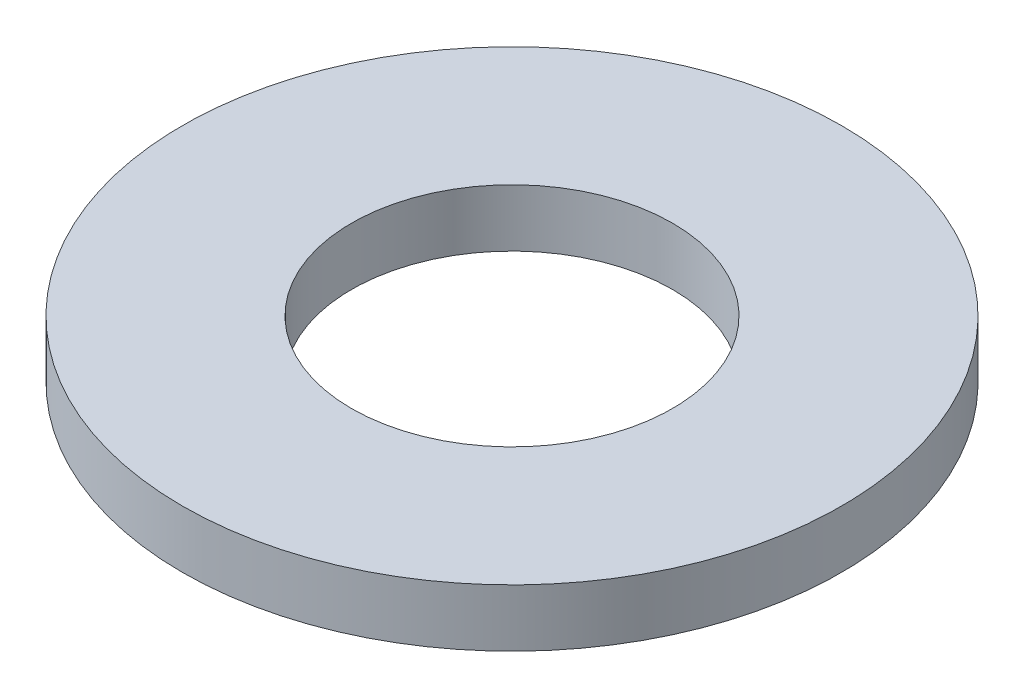
SolidWorks part; units mm, degrees
ref_plane "Front Plane" through (0, 0, 0) normal (0, 0, 1) x (1, 0, 0)
ref_plane "Top Plane" through (0, 0, 0) normal (0, 1, 0) x (1, 0, 0)
ref_plane "Right Plane" through (0, 0, 0) normal (1, 0, 0) x (0, 0, -1)
sketch "Sketch1" plane through (0, 0, 0) normal (0, 1, 0) x (1, 0, 0)
  circle A0 centre (0, 0) radius 97.5
  dimension "FLANGE_OD" = 195
extrude "Boss-Extrude1" add sketch "Sketch1" along normal blind 17
sketch "Sketch2" plane through (0, 0, 0) normal (0, 1, 0) x (1, 0, 0)
  circle A0 centre (0, 0) radius 47.5
  dimension "BORE_D" = 95
extrude "Cut-Extrude1" cut sketch "Sketch2" along normal through all
sketch "Sketch3" plane through (0, 17, 0) normal (0, 1, 0) x (1, 0, 0)
  circle A0 centre (0, 0) radius 41.7581 construction
  circle A1 centre (-41.7581, 0) radius 1.762
  dimension "BOLT_D" = 3.524
  dimension "BOLT_PCD" = 83.5161
extrude "Cut-Extrude2" cut sketch "Sketch3" against normal blind 12.5326 rebuild error yes
pattern_circular "CirPattern1" count 3 over 360 rebuild error yes
